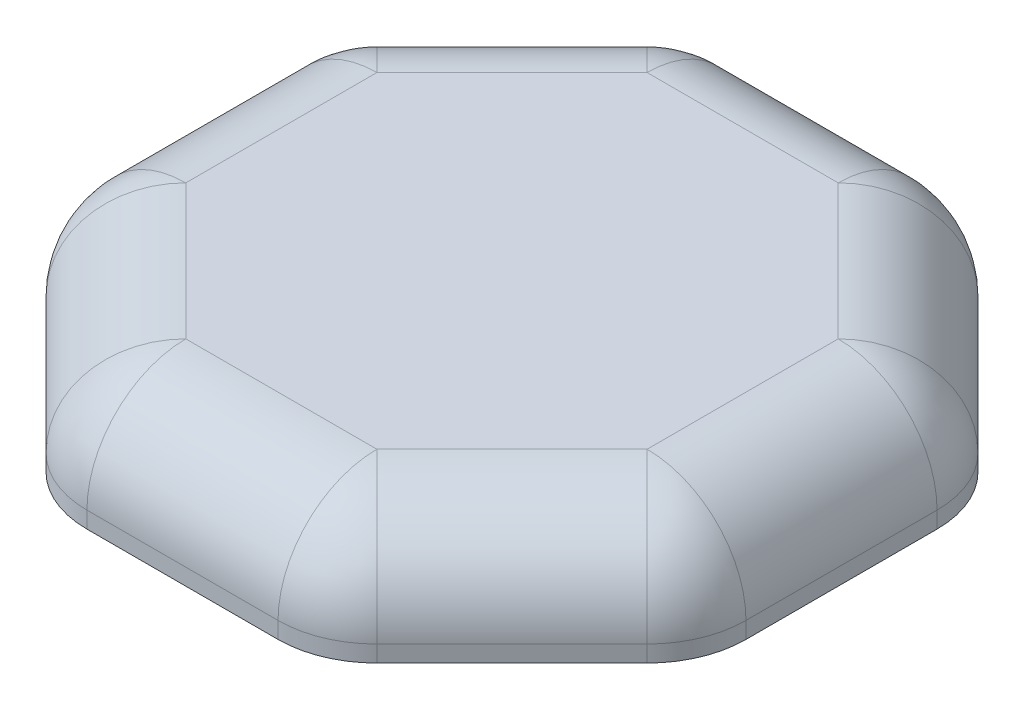
SolidWorks part; units mm, degrees
ref_plane "Front" through (0, 0, 0) normal (0, 0, 1) x (1, 0, 0)
ref_plane "Top" through (0, 0, 0) normal (0, 1, 0) x (1, 0, 0)
ref_plane "Right" through (0, 0, 0) normal (1, 0, 0) x (0, 0, -1)
sketch "Sketch1" plane through (0, 0, 0) normal (0, 1, 0) x (1, 0, 0)
  line L1 (100, 41.4214) -> (41.4214, 100)
  line L2 (41.4214, 100) -> (-41.4214, 100)
  line L3 (-41.4214, 100) -> (-100, 41.4214)
  line L4 (-100, 41.4214) -> (-100, -41.4214)
  line L5 (-100, -41.4214) -> (-41.4214, -100)
  line L6 (-41.4214, -100) -> (41.4214, -100)
  line L7 (41.4214, -100) -> (100, -41.4214)
  line L8 (100, -41.4214) -> (100, 41.4214)
  circle A0 centre (0, 0) radius 100 construction
  dimension "D1" = 200
extrude "Boss-Extrude1" add sketch "Sketch1" along normal blind 35 contours L3 L4 L5 L6 L7 L8 L1 L2
ref_axis "os bazy" through (0, 0, 0) along (0, 1, 0)
ref_plane "Plane1" through (0, 65, 0) normal (0, -1, 0) x (-1, 0, 0)
fillet "Fillet9" radius 30 8 edges at (-100, 17.5, 41.4214) (-100, 17.5, -41.4214) (-41.4214, 17.5, -100) (41.4214, 17.5, -100) (100, 17.5, -41.4214) (100, 17.5, 41.4214) (41.4214, 17.5, 100) (-41.4214, 17.5, 100)
fillet "Fillet12" radius 30 16 edges at (-97.7164, 35, 40.4755) (-100, 35, 0) (-97.7164, 35, -40.4755) (-70.7107, 35, -70.7107) (-40.4755, 35, -97.7164) (0, 35, -100) (40.4755, 35, -97.7164) (70.7107, 35, -70.7107) (97.7164, 35, -40.4755) (100, 35, 0) (97.7164, 35, 40.4755) (70.7107, 35, 70.7107) (40.4755, 35, 97.7164) (0, 35, 100) (-40.4755, 35, 97.7164) (-70.7107, 35, 70.7107)
shell "Shell2" thickness 2 removed face at (0, 0, 0)
